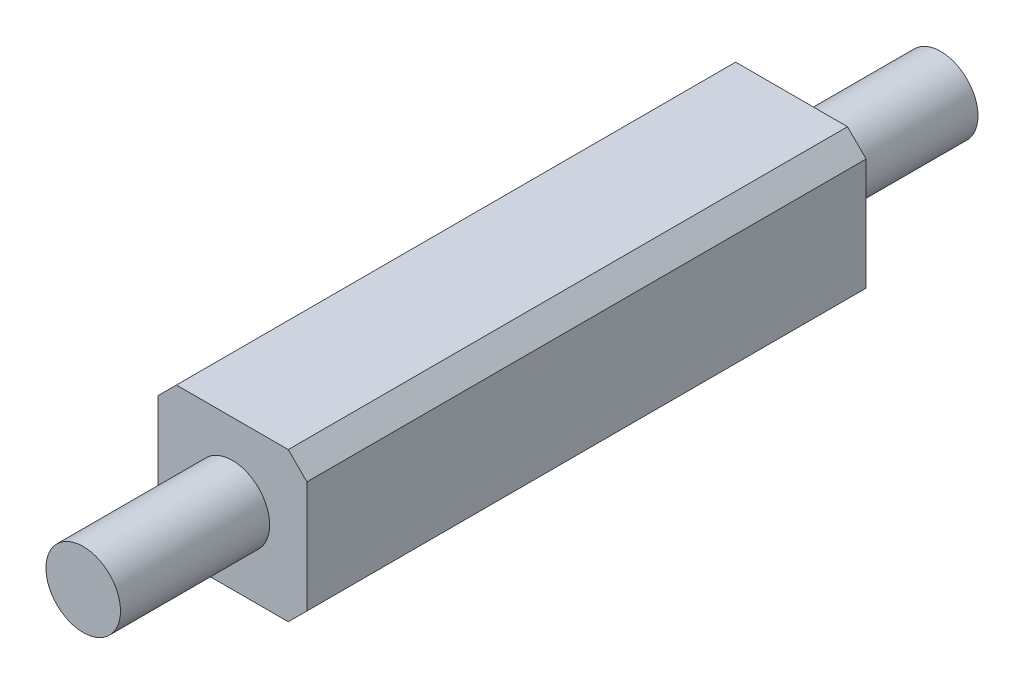
SolidWorks part; units mm, degrees
material "ABS"
ref_plane "Front Plane" through (0, 0, 0) normal (0, 0, 1) x (1, 0, 0)
ref_plane "Top Plane" through (0, 0, 0) normal (0, 1, 0) x (1, 0, 0)
ref_plane "Right Plane" through (0, 0, 0) normal (1, 0, 0) x (0, 0, -1)
sketch "Sketch1" plane through (0, 0, 0) normal (0, 1, 0) x (1, 0, 0)
  line L1 (-2, -7.5) -> (2, -7.5)
  line L2 (-2, -7.5) -> (-2, 7.5)
  line L3 (-2, 7.5) -> (2, 7.5)
  line L4 (2, -7.5) -> (2, 7.5)
  line L5 (-2, -7.5) -> (2, 7.5) construction
  line L6 (-2, 7.5) -> (2, -7.5) construction
  point P0 (0, 0)
  dimension "D1" = 15
  dimension "D2" = 4
extrude "Boss-Extrude1" add sketch "Sketch1" along normal blind 4
sketch "Sketch2" plane through (0, 0, 7.5) normal (0, 0, 1) x (1, 0, 0)
  line L3 (0, 0) -> (0, 4) construction
  line L4 (-2, 4) -> (2, 4) construction
  line L5 (-2, 2) -> (2, 2) construction
  line L6 (-2, 4) -> (-2, 0) construction
  line L7 (2, 4) -> (2, 0) construction
  circle A2 centre (0, 2) radius 1
  dimension "D1" = 2
extrude "Boss-Extrude2" add sketch "Sketch2" along normal blind 4 and the other way blind 19
chamfer "Chamfer1" distance 0.5 angle 45 4 edges at (-2, 0, 0) (-2, 4, 0) (2, 0, 0) (2, 4, 0)
